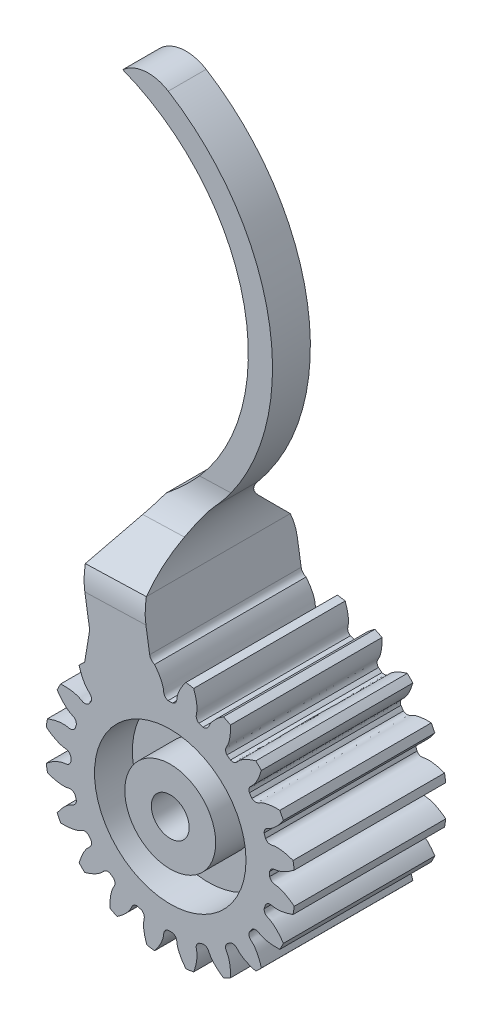
SolidWorks part; units mm, degrees
material "聚脂树脂"
ref_plane "前视基准面" through (0, 0, 0) normal (0, 0, 1) x (1, 0, 0)
ref_plane "上视基准面" through (0, 0, 0) normal (0, 1, 0) x (1, 0, 0)
ref_plane "右视基准面" through (0, 0, 0) normal (1, 0, 0) x (0, 0, -1)
other "Configuration Table"
sketch "草图1" plane through (0, 0, 0) normal (0, 0, 1) x (1, 0, 0)
  circle A0 centre (0, 0) radius 16.5
extrude "凸台-拉伸1" add sketch "草图1" along normal blind 20
ref_axis "基准轴1" through (0, 0, -1.5) along (0, 0, 1)
sketch "草图2" plane through (0, 0, 0) normal (0, 0, 1) x (1, 0, 0)
  line L0 (0, 0) -> (0, 16.5) construction
  circle A0 centre (0, 0) radius 16.5 construction
  arc A1 (0.29, 13.1218) -> (-0.29, 13.1218) centre (0, 0) ccw
  arc A2 (4.7717, 18.7474) -> (-4.7717, 18.7474) centre (0, 0) ccw
  spline S0 degree 3 poles (0.29, 13.1218) (0.9168, 13.3402) (0.8356, 13.7807) (0.9193, 14.205) (0.9283, 14.2463) (0.9395, 14.293) (0.9529, 14.3448) (0.969, 14.4018) (0.9878, 14.4638) (1.0095, 14.5309) (1.0345, 14.6028) (1.0629, 14.6795) (1.0948, 14.7608) (1.1305, 14.8467) (1.1702, 14.9371) (1.2141, 15.0317) (1.2623, 15.1305) (1.315, 15.2334) (1.3725, 15.3401) (1.4349, 15.4506) (1.5023, 15.5646) (1.575, 15.6821) (1.653, 15.8029) (1.7366, 15.9267) (1.826, 16.0534) (1.9211, 16.1829) (2.0223, 16.3149) (2.1296, 16.4493) (2.2432, 16.5859) (2.3632, 16.7244) (2.4897, 16.8646) (2.6229, 17.0065) (2.7628, 17.1496) (2.9095, 17.2939) (3.0632, 17.4391) (3.224, 17.585) (3.3918, 17.7313) (3.567, 17.8779) (3.7493, 18.0245) (3.9391, 18.1709) (4.1363, 18.3167) (4.4122, 18.5125) (4.6259, 18.6545) (4.7717, 18.7474) knots 0 0 0 0 0.165916 0.170906 0.176664 0.183189 0.190482 0.198542 0.207371 0.216967 0.22733 0.238462 0.250361 0.263027 0.276462 0.290664 0.305634 0.321371 0.337876 0.355149 0.37319 0.391998 0.411574 0.431917 0.453028 0.474907 0.497554 0.520968 0.54515 0.570099 0.595817 0.622302 0.649554 0.677575 0.706363 0.735918 0.766242 0.797333 0.829191 0.861818 0.895212 0.929373 1 1 1 1
  spline S1 degree 3 poles (-0.29, 13.1218) (-0.9168, 13.3402) (-0.8356, 13.7807) (-0.9193, 14.205) (-0.9283, 14.2463) (-0.9395, 14.293) (-0.9529, 14.3448) (-0.969, 14.4018) (-0.9878, 14.4638) (-1.0095, 14.5309) (-1.0345, 14.6028) (-1.0629, 14.6795) (-1.0948, 14.7608) (-1.1305, 14.8467) (-1.1702, 14.9371) (-1.2141, 15.0317) (-1.2623, 15.1305) (-1.315, 15.2334) (-1.3725, 15.3401) (-1.4349, 15.4506) (-1.5023, 15.5646) (-1.575, 15.6821) (-1.653, 15.8029) (-1.7366, 15.9267) (-1.826, 16.0534) (-1.9211, 16.1829) (-2.0223, 16.3149) (-2.1296, 16.4493) (-2.2432, 16.5859) (-2.3632, 16.7244) (-2.4897, 16.8646) (-2.6229, 17.0065) (-2.7628, 17.1496) (-2.9095, 17.2939) (-3.0632, 17.4391) (-3.224, 17.585) (-3.3918, 17.7313) (-3.567, 17.8779) (-3.7493, 18.0245) (-3.9391, 18.1709) (-4.1363, 18.3167) (-4.4122, 18.5125) (-4.6259, 18.6545) (-4.7717, 18.7474) knots 0 0 0 0 0.165916 0.170906 0.176664 0.183189 0.190482 0.198542 0.207371 0.216967 0.22733 0.238462 0.250361 0.263027 0.276462 0.290664 0.305634 0.321371 0.337876 0.355149 0.37319 0.391998 0.411574 0.431917 0.453028 0.474907 0.497554 0.520968 0.54515 0.570099 0.595817 0.622302 0.649554 0.677575 0.706363 0.735918 0.766242 0.797333 0.829191 0.861818 0.895212 0.929373 1 1 1 1
extrude "切除-拉伸1" cut sketch "草图2" along normal through all
pattern_circular "阵列(圆周)1" count 20 over 360 about axis through (0, 0, -1.5) along (0, 0, 1) of "切除-拉伸1"
sketch "草图3" plane through (0, 0, 0) normal (0, 0, 1) x (1, 0, 0)
  circle A0 centre (0, 0) radius 15 construction
  dimension "Dn" = 30
sketch "草图4" plane through (0, 0, 20) normal (0, 0, 1) x (1, 0, 0)
  line L0 (0, 0) -> (0, 24.252) construction
  line L1 (0, 0) -> (-4.1504, 26.2048) construction
  line L2 (-14.6667, -3.2847) -> (-22.6322, 47.0071) construction
  line L3 (-12.3599, 26.8976) -> (-7.9015, -1.2515)
  line L4 (-4.4584, 28.1491) -> (0, 0)
  line L5 (-15.1584, 78.5964) -> (-13.768, 74.7667)
  line L6 (-11.294, 12.029) -> (-10.6385, 16.029)
  line L7 (-3.0932, 16.2075) -> (-2.5812, 16.2969)
  line L8 (0, 0) -> (-34.8237, -5.5155) construction
  line L9 (-7.9015, -1.2515) -> (0, 0)
  circle A0 centre (0, 0) radius 12.5 construction
  circle A1 centre (-23.1908, 50.5343) radius 29.189 construction
  arc A2 (-2.0665, 16.3701) -> (-3.0932, 16.2075) centre (0, 0) ccw construction
  arc A3 (-4.4584, 28.1491) -> (-15.1584, 78.5964) centre (-23.1908, 50.5343) ccw
  circle A4 centre (-23.1908, 50.5343) radius 26 construction
  arc A6 (-12.3599, 26.8976) -> (-13.768, 74.7667) centre (-23.1908, 50.5343) ccw
  arc A8 (-3.7791, 12.5692) -> (-4.3306, 12.39) centre (0, 0) ccw construction
  arc A9 (-7.024, 14.9303) -> (-7.9502, 14.4584) centre (0, 0) ccw construction
  arc A10 (-7.4782, 10.7862) -> (-7.9474, 10.4453) centre (0, 0) ccw construction
  arc A12 (-3.7791, 12.5692) -> (-4.3306, 12.39) centre (0, 0) ccw
  arc A13 (-7.024, 14.9303) -> (-7.9502, 14.4584) centre (0, 0) ccw
  arc A14 (-7.4782, 10.7862) -> (-7.9474, 10.4453) centre (0, 0) ccw
  spline S0 degree 3 poles (1533.8481, 1281.675) (-100.0743, -100.0538) (-37.3462, 19.765) (-11.0168, 11.9483) (-10.7713, 11.8675) (-10.4966, 11.7648) (-10.2471, 11.6599) (-10.0224, 11.5547) (-9.822, 11.4509) (-9.671, 11.3649) (-9.5386, 11.2841) (-9.4441, 11.2225) (-9.3578, 11.1623) (-9.3008, 11.1209) (-9.2491, 11.0817) (-9.2026, 11.0451) (-9.1503, 11.0021) (-9.105, 10.9626) (-5.12, 7.2674) (-20.1054, -16.3486) (1244.1384, 1569.7336) knots -10.650201 -10.650201 -10.650201 -10.650201 0.502446 0.525093 0.568083 0.608002 0.644851 0.678629 0.709336 0.736973 0.749639 0.77267 0.783033 0.792629 0.801458 0.809518 0.816811 0.829094 0.834084 3.036535 3.036535 3.036535 3.036535 only from (-11.294, 12.029) to (-7.9474, 10.4453) construction
  spline S1 degree 3 poles (-2001.2932, -83.8658) (25.0446, 6.6561) (-2.87, 8.4138) (-3.5171, 13.8097) (-3.5224, 13.8696) (-3.5265, 13.9372) (-3.5289, 13.9963) (-3.5307, 14.0865) (-3.5293, 14.2134) (-3.5206, 14.3824) (-3.5033, 14.5733) (-3.4754, 14.7858) (-3.4352, 15.0192) (-3.381, 15.2729) (-3.3111, 15.5461) (-3.2398, 15.7847) (-3.1737, 15.9845) (5.9613, 41.8314) (139.7678, 22.1516) (-1938.4783, -487.5615) knots -2.036559 -2.036559 -2.036559 -2.036559 0.165916 0.170906 0.183189 0.190482 0.198542 0.207371 0.22733 0.250361 0.276462 0.305634 0.337876 0.37319 0.411574 0.453028 0.474907 0.497554 11.650216 11.650216 11.650216 11.650216 only from (-3.7791, 12.5692) to (-3.0932, 16.2075) construction
  spline S2 degree 3 poles (1854.8356, 744.9602) (-126.0947, -64.2322) (-29.4106, 30.3383) (-6.7853, 14.7679) (-6.5768, 14.6152) (-6.3474, 14.4326) (-6.1425, 14.2557) (-5.9612, 14.0862) (-5.8028, 13.9257) (-5.6857, 13.7971) (-5.5848, 13.6794) (-5.514, 13.5916) (-5.4504, 13.5077) (-5.409, 13.4507) (-5.3719, 13.3975) (-5.3391, 13.3482) (-5.3027, 13.2912) (-5.2717, 13.2396) (-2.6237, 8.4939) (-24.1734, -9.3355) (1668.3203, 1108.4455) knots -10.650201 -10.650201 -10.650201 -10.650201 0.502446 0.525093 0.568083 0.608002 0.644851 0.678629 0.709336 0.736973 0.749639 0.77267 0.783033 0.792629 0.801458 0.809518 0.816811 0.829094 0.834084 3.036535 3.036535 3.036535 3.036535 only from (-7.024, 14.9303) to (-4.3306, 12.39) construction
  spline S3 degree 3 poles (-1877.4269, -698.1947) (21.762, 14.0695) (-5.3295, 7.1151) (-7.6124, 12.047) (-7.636, 12.1023) (-7.6607, 12.1653) (-7.6812, 12.2208) (-7.7108, 12.3061) (-7.7487, 12.4272) (-7.7927, 12.5905) (-7.8352, 12.7775) (-7.8743, 12.9882) (-7.9082, 13.2226) (-7.9351, 13.4806) (-7.9531, 13.762) (-7.959, 14.011) (-7.9578, 14.2215) (-7.257, 41.6261) (126.0819, 64.2581) (-1692.9376, -1062.7213) knots -2.036559 -2.036559 -2.036559 -2.036559 0.165916 0.170906 0.183189 0.190482 0.198542 0.207371 0.22733 0.250361 0.276462 0.305634 0.337876 0.37319 0.411574 0.453028 0.474907 0.497554 11.650216 11.650216 11.650216 11.650216 only from (-7.4782, 10.7862) to (-7.9502, 14.4584) construction
  spline S4 degree 3 poles (-3.7791, 12.5692) (-3.2504, 12.9706) (-3.4637, 13.3644) (-3.5171, 13.8097) (-3.5224, 13.8696) (-3.5265, 13.9372) (-3.5289, 13.9963) (-3.5307, 14.0865) (-3.5293, 14.2134) (-3.5206, 14.3824) (-3.5033, 14.5733) (-3.4754, 14.7858) (-3.4352, 15.0192) (-3.381, 15.2729) (-3.3111, 15.5461) (-3.224, 15.8378) (-3.1479, 16.0599) (-3.1017, 16.1848) (-3.0932, 16.2075) knots 0 0 0 0 0.165916 0.170906 0.183189 0.190482 0.198542 0.207371 0.22733 0.250361 0.276462 0.305634 0.337876 0.37319 0.411574 0.453028 0.497554 0.507432 0.507432 0.507432 0.507432
  spline S5 degree 3 poles (-7.024, 14.9303) (-6.9129, 14.8568) (-6.7202, 14.7228) (-6.459, 14.5233) (-6.2419, 14.3433) (-6.0489, 14.1699) (-5.8792, 14.0047) (-5.7318, 13.8492) (-5.6234, 13.7255) (-5.5309, 13.613) (-5.4664, 13.5298) (-5.409, 13.4507) (-5.3719, 13.3975) (-5.3391, 13.3482) (-5.3027, 13.2912) (-5.2717, 13.2396) (-5.0532, 12.848) (-4.9943, 12.404) (-4.3306, 12.39) knots 0.492568 0.492568 0.492568 0.492568 0.546972 0.588426 0.62681 0.662124 0.694366 0.723538 0.749639 0.761538 0.783033 0.792629 0.801458 0.809518 0.816811 0.829094 0.834084 1 1 1 1
  spline S6 degree 3 poles (-7.4782, 10.7862) (-7.0995, 11.3313) (-7.424, 11.64) (-7.6124, 12.047) (-7.636, 12.1023) (-7.6607, 12.1653) (-7.6812, 12.2208) (-7.7108, 12.3061) (-7.7487, 12.4272) (-7.7927, 12.5905) (-7.8352, 12.7775) (-7.8743, 12.9882) (-7.9082, 13.2226) (-7.9351, 13.4806) (-7.9531, 13.762) (-7.9603, 14.0664) (-7.9566, 14.3011) (-7.9513, 14.4342) (-7.9502, 14.4584) knots 0 0 0 0 0.165916 0.170906 0.183189 0.190482 0.198542 0.207371 0.22733 0.250361 0.276462 0.305634 0.337876 0.37319 0.411574 0.453028 0.497554 0.507432 0.507432 0.507432 0.507432
  spline S7 degree 3 poles (-11.294, 12.029) (-11.1656, 11.9934) (-10.9409, 11.9255) (-10.6308, 11.8165) (-10.3687, 11.7125) (-10.1316, 11.6072) (-9.9192, 11.5025) (-9.7309, 11.4002) (-9.5896, 11.316) (-9.4669, 11.2376) (-9.3798, 11.1783) (-9.3008, 11.1209) (-9.2491, 11.0817) (-9.2026, 11.0451) (-9.1503, 11.0021) (-9.105, 10.9626) (-8.7761, 10.6576) (-8.5829, 10.2536) (-7.9474, 10.4453) knots 0.492568 0.492568 0.492568 0.492568 0.546972 0.588426 0.62681 0.662124 0.694366 0.723538 0.749639 0.761538 0.783033 0.792629 0.801458 0.809518 0.816811 0.829094 0.834084 1 1 1 1
  dimension "D6" = 52
  dimension "D7" = 76
  dimension "D5" = 28.5
  dimension "D10" = 25
  dimension "D9" = 80
  dimension "D1" = 9
  dimension "D2" = 15
  dimension "D3" = 8
  dimension "D4" = 28.5
  dimension "D8" = 4
extrude "凸台-拉伸2" add sketch "草图4" against normal blind 20 contours S7 A14 S6 A13 S5 A12 S4 L7 A6 | S7 region at (3.5117, 51.3198, 20) region at (-10.6183, 13.2048, 20)
fillet "圆角1" radius 1 1 edges
fillet "圆角2" radius 5 1 edges at (-15.1584, 78.5964, 10)
fillet "圆角4" radius 10 1 edges at (-4.4584, 28.1491, 10)
sketch "草图5" plane through (0, 0, 20) normal (0, 0, 1) x (1, 0, 0)
  circle A0 centre (0, 0) radius 2.5
  dimension "D1" = 5
extrude "切除-拉伸2" cut sketch "草图5" against normal blind 20
chamfer "倒角1" distance 5 angle 45 1 edges at (-12.3599, 26.8976, 10) first distance on face at (-11.4992, 21.4633, 10)
sketch "草图7" plane through (0, 0, 0) normal (0, 0, -1) x (-1, 0, 0)
  circle A0 centre (0, 0) radius 10
  dimension "D1" = 20
extrude "切除-拉伸3" cut sketch "草图7" against normal blind 3
sketch "草图8" plane through (0, 0, 20) normal (0, 0, 1) x (1, 0, 0)
  circle A0 centre (0, 0) radius 6
  circle A1 centre (0, 0) radius 10
  dimension "D1" = 12
  dimension "D2" = 20
extrude "切除-拉伸4" cut sketch "草图8" against normal blind 5
sketch "草图9" plane through (0, 0, 0) normal (1, 0, 0) x (0, 0, -1)
  line L0 (-10, 46.7) -> (-10, 64.7) construction
  line L5 (-13, 46.7) -> (-13, 64.7)
  line L6 (-7, 46.7) -> (-7, 64.7)
  line L7 (0, 31.2457) -> (0, 75.3118) construction
  arc A0 (-13, 46.7) -> (-7, 46.7) centre (-10, 46.7) ccw
  arc A1 (-7, 64.7) -> (-13, 64.7) centre (-10, 64.7) ccw
  point P2 (-10, 55.7)
  dimension "D2" = 3
  dimension "D1" = 18
  dimension "D3" = 10
  dimension "D4" = 55.7
sketch "草图10" plane through (0, 0, 0) normal (0, 0, -1) x (-1, 0, 0)
  line L0 (3.6544, 23.0732) -> (11.7149, 22.8255)
  line L4 (10.6385, 16.029) -> (11.7149, 22.8255)
  line L5 (11.7149, 22.8255) -> (7.3378, 29.9264)
  line L6 (3.6544, 23.0732) -> (2.7171, 17.1551)
  line L7 (11.294, 12.029) -> (10.6385, 16.029)
  line L8 (10.6385, 16.029) -> (11.7149, 22.8255)
  line L9 (11.7149, 22.8255) -> (7.3378, 29.9264)
  line L10 (3.6544, 23.0732) -> (2.7171, 17.1551)
  line L11 (11.294, 12.029) -> (10.6385, 16.029)
  arc A41 (13.768, 74.7667) -> (7.3378, 29.9264) centre (23.1908, 50.5343) ccw
  arc A42 (13.768, 74.7667) -> (7.7611, 75.3118) centre (10.4042, 71.0674) ccw
  arc A43 (7.7611, 75.3118) -> (1.283, 31.2457) centre (23.1908, 50.5343) ccw
  arc A44 (3.6544, 23.0732) -> (1.283, 31.2457) centre (-6.2224, 24.6376) ccw
  arc A45 (2.0665, 16.3701) -> (2.7171, 17.1551) centre (1.7294, 17.3115) ccw
  arc A46 (0.29, 13.1218) -> (-0.29, 13.1218) centre (0, 0) ccw
  arc A47 (-2.0665, 16.3701) -> (-3.0932, 16.2075) centre (0, 0) ccw
  arc A48 (-3.7791, 12.5692) -> (-4.3306, 12.39) centre (0, 0) ccw
  arc A49 (-7.024, 14.9303) -> (-7.9502, 14.4584) centre (0, 0) ccw
  arc A50 (-7.4782, 10.7862) -> (-7.9474, 10.4453) centre (0, 0) ccw
  arc A51 (-11.294, 12.029) -> (-12.029, 11.294) centre (0, 0) ccw
  arc A52 (-10.4453, 7.9474) -> (-10.7862, 7.4782) centre (0, 0) ccw
  arc A53 (-14.4584, 7.9502) -> (-14.9303, 7.024) centre (0, 0) ccw
  arc A54 (-12.39, 4.3306) -> (-12.5692, 3.7791) centre (0, 0) ccw
  arc A55 (-16.2075, 3.0932) -> (-16.3701, 2.0665) centre (0, 0) ccw
  arc A56 (-13.1218, 0.29) -> (-13.1218, -0.29) centre (0, 0) ccw
  arc A57 (-16.3701, -2.0665) -> (-16.2075, -3.0932) centre (0, 0) ccw
  arc A58 (-12.5692, -3.7791) -> (-12.39, -4.3306) centre (0, 0) ccw
  arc A59 (-14.9303, -7.024) -> (-14.4584, -7.9502) centre (0, 0) ccw
  arc A60 (-10.7862, -7.4782) -> (-10.4453, -7.9474) centre (0, 0) ccw
  arc A61 (-12.029, -11.294) -> (-11.294, -12.029) centre (0, 0) ccw
  arc A62 (-7.9474, -10.4453) -> (-7.4782, -10.7862) centre (0, 0) ccw
  arc A63 (-7.9502, -14.4584) -> (-7.024, -14.9303) centre (0, 0) ccw
  arc A64 (-4.3306, -12.39) -> (-3.7791, -12.5692) centre (0, 0) ccw
  arc A65 (-3.0932, -16.2075) -> (-2.0665, -16.3701) centre (0, 0) ccw
  arc A66 (-0.29, -13.1218) -> (0.29, -13.1218) centre (0, 0) ccw
  arc A67 (2.0665, -16.3701) -> (3.0932, -16.2075) centre (0, 0) ccw
  arc A68 (3.7791, -12.5692) -> (4.3306, -12.39) centre (0, 0) ccw
  arc A69 (7.024, -14.9303) -> (7.9502, -14.4584) centre (0, 0) ccw
  arc A70 (7.4782, -10.7862) -> (7.9474, -10.4453) centre (0, 0) ccw
  arc A71 (11.294, -12.029) -> (12.029, -11.294) centre (0, 0) ccw
  arc A72 (10.4453, -7.9474) -> (10.7862, -7.4782) centre (0, 0) ccw
  arc A73 (14.4584, -7.9502) -> (14.9303, -7.024) centre (0, 0) ccw
  arc A74 (12.39, -4.3306) -> (12.5692, -3.7791) centre (0, 0) ccw
  arc A75 (16.2075, -3.0932) -> (16.3701, -2.0665) centre (0, 0) ccw
  arc A76 (13.1218, -0.29) -> (13.1218, 0.29) centre (0, 0) ccw
  arc A77 (16.3701, 2.0665) -> (16.2075, 3.0932) centre (0, 0) ccw
  arc A78 (12.5692, 3.7791) -> (12.39, 4.3306) centre (0, 0) ccw
  arc A79 (14.9303, 7.024) -> (14.4584, 7.9502) centre (0, 0) ccw
  arc A80 (10.7862, 7.4782) -> (10.4453, 7.9474) centre (0, 0) ccw
  arc A81 (12.029, 11.294) -> (11.294, 12.029) centre (0, 0) ccw
  arc A82 (13.768, 74.7667) -> (7.3378, 29.9264) centre (23.1908, 50.5343) ccw
  arc A83 (13.768, 74.7667) -> (7.7611, 75.3118) centre (10.4042, 71.0674) ccw
  arc A84 (7.7611, 75.3118) -> (1.283, 31.2457) centre (23.1908, 50.5343) ccw
  arc A85 (3.6544, 23.0732) -> (1.283, 31.2457) centre (-6.2224, 24.6376) ccw
  arc A86 (2.0665, 16.3701) -> (2.7171, 17.1551) centre (1.7294, 17.3115) ccw
  arc A87 (0.29, 13.1218) -> (-0.29, 13.1218) centre (0, 0) ccw
  arc A88 (-2.0665, 16.3701) -> (-3.0932, 16.2075) centre (0, 0) ccw
  arc A89 (-3.7791, 12.5692) -> (-4.3306, 12.39) centre (0, 0) ccw
  arc A90 (-7.024, 14.9303) -> (-7.9502, 14.4584) centre (0, 0) ccw
  arc A91 (-7.4782, 10.7862) -> (-7.9474, 10.4453) centre (0, 0) ccw
  arc A92 (-11.294, 12.029) -> (-12.029, 11.294) centre (0, 0) ccw
  arc A93 (-10.4453, 7.9474) -> (-10.7862, 7.4782) centre (0, 0) ccw
  arc A94 (-14.4584, 7.9502) -> (-14.9303, 7.024) centre (0, 0) ccw
  arc A95 (-12.39, 4.3306) -> (-12.5692, 3.7791) centre (0, 0) ccw
  arc A96 (-16.2075, 3.0932) -> (-16.3701, 2.0665) centre (0, 0) ccw
  arc A97 (-13.1218, 0.29) -> (-13.1218, -0.29) centre (0, 0) ccw
  arc A98 (-16.3701, -2.0665) -> (-16.2075, -3.0932) centre (0, 0) ccw
  arc A99 (-12.5692, -3.7791) -> (-12.39, -4.3306) centre (0, 0) ccw
  arc A100 (-14.9303, -7.024) -> (-14.4584, -7.9502) centre (0, 0) ccw
  arc A101 (-10.7862, -7.4782) -> (-10.4453, -7.9474) centre (0, 0) ccw
  arc A102 (-12.029, -11.294) -> (-11.294, -12.029) centre (0, 0) ccw
  arc A103 (-7.9474, -10.4453) -> (-7.4782, -10.7862) centre (0, 0) ccw
  arc A104 (-7.9502, -14.4584) -> (-7.024, -14.9303) centre (0, 0) ccw
  arc A105 (-4.3306, -12.39) -> (-3.7791, -12.5692) centre (0, 0) ccw
  arc A106 (-3.0932, -16.2075) -> (-2.0665, -16.3701) centre (0, 0) ccw
  arc A107 (-0.29, -13.1218) -> (0.29, -13.1218) centre (0, 0) ccw
  arc A108 (2.0665, -16.3701) -> (3.0932, -16.2075) centre (0, 0) ccw
  arc A109 (3.7791, -12.5692) -> (4.3306, -12.39) centre (0, 0) ccw
  arc A110 (7.024, -14.9303) -> (7.9502, -14.4584) centre (0, 0) ccw
  arc A111 (7.4782, -10.7862) -> (7.9474, -10.4453) centre (0, 0) ccw
  arc A112 (11.294, -12.029) -> (12.029, -11.294) centre (0, 0) ccw
  arc A113 (10.4453, -7.9474) -> (10.7862, -7.4782) centre (0, 0) ccw
  arc A114 (14.4584, -7.9502) -> (14.9303, -7.024) centre (0, 0) ccw
  arc A115 (12.39, -4.3306) -> (12.5692, -3.7791) centre (0, 0) ccw
  arc A116 (16.2075, -3.0932) -> (16.3701, -2.0665) centre (0, 0) ccw
  arc A117 (13.1218, -0.29) -> (13.1218, 0.29) centre (0, 0) ccw
  arc A118 (16.3701, 2.0665) -> (16.2075, 3.0932) centre (0, 0) ccw
  arc A119 (12.5692, 3.7791) -> (12.39, 4.3306) centre (0, 0) ccw
  arc A120 (14.9303, 7.024) -> (14.4584, 7.9502) centre (0, 0) ccw
  arc A121 (10.7862, 7.4782) -> (10.4453, 7.9474) centre (0, 0) ccw
  arc A122 (12.029, 11.294) -> (11.294, 12.029) centre (0, 0) ccw
  spline S36 degree 3 poles (-3988.5857, 284.068) (202.7385, -48.5513) (20.2552, 42.738) (1.6549, 15.8084) (1.5041, 15.5702) (1.3741, 15.3456) (1.2638, 15.1361) (1.1716, 14.9426) (1.1068, 14.7914) (1.0536, 14.6559) (1.018, 14.5568) (0.9878, 14.4638) (0.969, 14.4018) (0.9529, 14.3448) (0.9359, 14.2793) (0.9224, 14.2207) (-0.397, 7.5331) (40.9433, -7.0017) (-3856.5787, 1071.6934) knots -12.739394 -12.739394 -12.739394 -12.739394 0.546972 0.588426 0.62681 0.662124 0.694366 0.723538 0.749639 0.761538 0.783033 0.792629 0.801458 0.809518 0.816811 0.829094 0.834084 3.601006 3.601006 3.601006 3.601006 only from (2.0665, 16.3701) to (0.29, 13.1218)
  spline S37 degree 3 poles (3856.2698, 1071.6079) (-40.9411, -7.001) (0.3969, 7.5333) (-0.9224, 14.2207) (-0.9359, 14.2793) (-0.9529, 14.3448) (-0.969, 14.4018) (-0.9951, 14.4881) (-1.0357, 14.6084) (-1.0961, 14.7664) (-1.1716, 14.9426) (-1.2638, 15.1361) (-1.3741, 15.3456) (-1.5041, 15.5702) (-1.6549, 15.8084) (-1.828, 16.0589) (-22.7654, 43.9229) (-212.0574, -60.1846) (3987.5666, 298.067) knots -2.600932 -2.600932 -2.600932 -2.600932 0.165916 0.170906 0.183189 0.190482 0.198542 0.207371 0.22733 0.250361 0.276462 0.305634 0.337876 0.37319 0.411574 0.453028 0.497554 14.645505 14.645505 14.645505 14.645505 only from (-0.29, 13.1218) to (-2.0665, 16.3701)
  spline S38 degree 3 poles (-3881.1522, -962.376) (207.8189, 16.4746) (6.057, 46.9055) (-3.3111, 15.5461) (-3.381, 15.2729) (-3.4352, 15.0192) (-3.4754, 14.7858) (-3.5033, 14.5733) (-3.5182, 14.4095) (-3.5269, 14.2641) (-3.5302, 14.1589) (-3.5302, 14.0612) (-3.5289, 13.9963) (-3.5265, 13.9372) (-3.5224, 13.8696) (-3.5171, 13.8097) (-2.7054, 7.0417) (41.1031, 5.9931) (-3998.9957, -172.5074) knots -12.739394 -12.739394 -12.739394 -12.739394 0.546972 0.588426 0.62681 0.662124 0.694366 0.723538 0.749639 0.761538 0.783033 0.792629 0.801458 0.809518 0.816811 0.829094 0.834084 3.601006 3.601006 3.601006 3.601006 only from (-3.0932, 16.2075) to (-3.7791, 12.5692)
  spline S39 degree 3 poles (3336.3854, 2210.8126) (-36.7739, -19.3098) (-1.9504, 7.2872) (-5.2717, 13.2396) (-5.3027, 13.2912) (-5.3391, 13.3482) (-5.3719, 13.3975) (-5.4235, 13.4715) (-5.4992, 13.5733) (-5.6055, 13.705) (-5.7318, 13.8492) (-5.8792, 14.0047) (-6.0489, 14.1699) (-6.2419, 14.3433) (-6.459, 14.5233) (-6.701, 14.7081) (-35.2241, 34.7383) (-183.0805, -122.7683) (3700.2934, 1515.7044) knots -2.600932 -2.600932 -2.600932 -2.600932 0.165916 0.170906 0.183189 0.190482 0.198542 0.207371 0.22733 0.250361 0.276462 0.305634 0.337876 0.37319 0.411574 0.453028 0.497554 14.645505 14.645505 14.645505 14.645505 only from (-4.3306, 12.39) to (-7.024, 14.9303)
  spline S40 degree 3 poles (-3393.8046, -2114.616) (192.5566, 79.8879) (-8.734, 46.4815) (-7.9531, 13.762) (-7.9351, 13.4806) (-7.9082, 13.2226) (-7.8743, 12.9882) (-7.8352, 12.7775) (-7.7988, 12.6171) (-7.7621, 12.4761) (-7.7327, 12.375) (-7.7025, 12.2821) (-7.6812, 12.2208) (-7.6607, 12.1653) (-7.636, 12.1023) (-7.6124, 12.047) (-4.749, 5.8611) (37.2394, 18.4014) (-3749.9632, -1399.8219) knots -12.739394 -12.739394 -12.739394 -12.739394 0.546972 0.588426 0.62681 0.662124 0.694366 0.723538 0.749639 0.761538 0.783033 0.792629 0.801458 0.809518 0.816811 0.829094 0.834084 3.601006 3.601006 3.601006 3.601006 only from (-7.9502, 14.4584) to (-7.4782, 10.7862)
  spline S41 degree 3 poles (2489.9125, 3133.6075) (-29.007, -29.7285) (-4.1068, 6.3279) (-9.105, 10.9626) (-9.1503, 11.0021) (-9.2026, 11.0451) (-9.2491, 11.0817) (-9.321, 11.1362) (-9.4245, 11.2097) (-9.5662, 11.302) (-9.7309, 11.4002) (-9.9192, 11.5025) (-10.1316, 11.6072) (-10.3687, 11.7125) (-10.6308, 11.8165) (-10.9181, 11.9175) (-44.2348, 22.1532) (-136.1824, -173.3346) (3050.8097, 2584.9741) knots -2.600932 -2.600932 -2.600932 -2.600932 0.165916 0.170906 0.183189 0.190482 0.198542 0.207371 0.22733 0.250361 0.276462 0.305634 0.337876 0.37319 0.411574 0.453028 0.497554 14.645505 14.645505 14.645505 14.645505 only from (-7.9474, 10.4453) to (-11.294, 12.029)
  spline S42 degree 3 poles (-2574.2477, -3059.8626) (158.4455, 135.4812) (-22.6701, 41.5076) (-11.8165, 10.6308) (-11.7125, 10.3687) (-11.6072, 10.1316) (-11.5025, 9.9192) (-11.4002, 9.7309) (-11.316, 9.5896) (-11.2376, 9.4669) (-11.1783, 9.3798) (-11.1209, 9.3008) (-11.0817, 9.2491) (-11.0451, 9.2026) (-11.0021, 9.1503) (-10.9626, 9.105) (-6.3277, 4.1067) (29.7304, 29.0083) (-3133.8582, -2490.1121) knots -12.739394 -12.739394 -12.739394 -12.739394 0.546972 0.588426 0.62681 0.662124 0.694366 0.723538 0.749639 0.761538 0.783033 0.792629 0.801458 0.809518 0.816811 0.829094 0.834084 3.601006 3.601006 3.601006 3.601006 only from (-12.029, 11.294) to (-10.4453, 7.9474)
  spline S43 degree 3 poles (1399.7095, 3749.6631) (-18.4007, -37.2371) (-5.8612, 4.7491) (-12.047, 7.6124) (-12.1023, 7.636) (-12.1653, 7.6607) (-12.2208, 7.6812) (-12.3061, 7.7108) (-12.4272, 7.7487) (-12.5905, 7.7927) (-12.7775, 7.8352) (-12.9882, 7.8743) (-13.2226, 7.9082) (-13.4806, 7.9351) (-13.762, 7.9531) (-14.0664, 7.9603) (-48.9155, 7.3996) (-75.9539, -206.9336) (2102.6915, 3401.2085) knots -2.600932 -2.600932 -2.600932 -2.600932 0.165916 0.170906 0.183189 0.190482 0.198542 0.207371 0.22733 0.250361 0.276462 0.305634 0.337876 0.37319 0.411574 0.453028 0.497554 14.645505 14.645505 14.645505 14.645505 only from (-10.7862, 7.4782) to (-14.4584, 7.9502)
  spline S44 degree 3 poles (-1502.7055, -3705.5886) (108.8246, 177.8126) (-34.3871, 32.4706) (-14.5233, 6.459) (-14.3433, 6.2419) (-14.1699, 6.0489) (-14.0047, 5.8792) (-13.8492, 5.7318) (-13.7255, 5.6234) (-13.613, 5.5309) (-13.5298, 5.4664) (-13.4507, 5.409) (-13.3975, 5.3719) (-13.3482, 5.3391) (-13.2912, 5.3027) (-13.2396, 5.2717) (-7.2871, 1.9503) (19.3112, 36.7758) (-2210.9893, -3336.6528) knots -12.739394 -12.739394 -12.739394 -12.739394 0.546972 0.588426 0.62681 0.662124 0.694366 0.723538 0.749639 0.761538 0.783033 0.792629 0.801458 0.809518 0.816811 0.829094 0.834084 3.601006 3.601006 3.601006 3.601006 only from (-14.9303, 7.024) to (-12.39, 4.3306)
  spline S45 degree 3 poles (172.4932, 3998.6755) (-5.9932, -41.1008) (-7.0419, 2.7054) (-13.8097, 3.5171) (-13.8696, 3.5224) (-13.9372, 3.5265) (-13.9963, 3.5289) (-14.0865, 3.5307) (-14.2134, 3.5293) (-14.3824, 3.5206) (-14.5733, 3.5033) (-14.7858, 3.4754) (-15.0192, 3.4352) (-15.2729, 3.381) (-15.5461, 3.3111) (-15.8378, 3.224) (-48.808, -8.0783) (-8.2904, -220.2766) (948.7472, 3884.5089) knots -2.600932 -2.600932 -2.600932 -2.600932 0.165916 0.170906 0.183189 0.190482 0.198542 0.207371 0.22733 0.250361 0.276462 0.305634 0.337876 0.37319 0.411574 0.453028 0.497554 14.645505 14.645505 14.645505 14.645505 only from (-12.5692, 3.7791) to (-16.2075, 3.0932)
  spline S46 degree 3 poles (-284.068, -3988.5857) (48.5513, 202.7385) (-42.738, 20.2552) (-15.8084, 1.6549) (-15.5702, 1.5041) (-15.3456, 1.3741) (-15.1361, 1.2638) (-14.9426, 1.1716) (-14.7914, 1.1068) (-14.6559, 1.0536) (-14.5568, 1.018) (-14.4638, 0.9878) (-14.4018, 0.969) (-14.3448, 0.9529) (-14.2793, 0.9359) (-14.2207, 0.9224) (-7.5331, -0.397) (7.0017, 40.9433) (-1071.6934, -3856.5787) knots -12.739394 -12.739394 -12.739394 -12.739394 0.546972 0.588426 0.62681 0.662124 0.694366 0.723538 0.749639 0.761538 0.783033 0.792629 0.801458 0.809518 0.816811 0.829094 0.834084 3.601006 3.601006 3.601006 3.601006 only from (-16.3701, 2.0665) to (-13.1218, 0.29)
  spline S47 degree 3 poles (-1071.6079, 3856.2698) (7.001, -40.9411) (-7.5333, 0.3969) (-14.2207, -0.9224) (-14.2793, -0.9359) (-14.3448, -0.9529) (-14.4018, -0.969) (-14.4881, -0.9951) (-14.6084, -1.0357) (-14.7664, -1.0961) (-14.9426, -1.1716) (-15.1361, -1.2638) (-15.3456, -1.3741) (-15.5702, -1.5041) (-15.8084, -1.6549) (-16.0589, -1.828) (-43.9229, -22.7654) (60.1846, -212.0574) (-298.067, 3987.5666) knots -2.600932 -2.600932 -2.600932 -2.600932 0.165916 0.170906 0.183189 0.190482 0.198542 0.207371 0.22733 0.250361 0.276462 0.305634 0.337876 0.37319 0.411574 0.453028 0.497554 14.645505 14.645505 14.645505 14.645505 only from (-13.1218, -0.29) to (-16.3701, -2.0665)
  spline S48 degree 3 poles (962.376, -3881.1522) (-16.4746, 207.8189) (-46.9055, 6.057) (-15.5461, -3.3111) (-15.2729, -3.381) (-15.0192, -3.4352) (-14.7858, -3.4754) (-14.5733, -3.5033) (-14.4095, -3.5182) (-14.2641, -3.5269) (-14.1589, -3.5302) (-14.0612, -3.5302) (-13.9963, -3.5289) (-13.9372, -3.5265) (-13.8696, -3.5224) (-13.8097, -3.5171) (-7.0417, -2.7054) (-5.9931, 41.1031) (172.5074, -3998.9957) knots -12.739394 -12.739394 -12.739394 -12.739394 0.546972 0.588426 0.62681 0.662124 0.694366 0.723538 0.749639 0.761538 0.783033 0.792629 0.801458 0.809518 0.816811 0.829094 0.834084 3.601006 3.601006 3.601006 3.601006 only from (-16.2075, -3.0932) to (-12.5692, -3.7791)
  spline S49 degree 3 poles (-2210.8126, 3336.3854) (19.3098, -36.7739) (-7.2872, -1.9504) (-13.2396, -5.2717) (-13.2912, -5.3027) (-13.3482, -5.3391) (-13.3975, -5.3719) (-13.4715, -5.4235) (-13.5733, -5.4992) (-13.705, -5.6055) (-13.8492, -5.7318) (-14.0047, -5.8792) (-14.1699, -6.0489) (-14.3433, -6.2419) (-14.5233, -6.459) (-14.7081, -6.701) (-34.7383, -35.2241) (122.7683, -183.0805) (-1515.7044, 3700.2934) knots -2.600932 -2.600932 -2.600932 -2.600932 0.165916 0.170906 0.183189 0.190482 0.198542 0.207371 0.22733 0.250361 0.276462 0.305634 0.337876 0.37319 0.411574 0.453028 0.497554 14.645505 14.645505 14.645505 14.645505 only from (-12.39, -4.3306) to (-14.9303, -7.024)
  spline S50 degree 3 poles (2114.616, -3393.8046) (-79.8879, 192.5566) (-46.4815, -8.734) (-13.762, -7.9531) (-13.4806, -7.9351) (-13.2226, -7.9082) (-12.9882, -7.8743) (-12.7775, -7.8352) (-12.6171, -7.7988) (-12.4761, -7.7621) (-12.375, -7.7327) (-12.2821, -7.7025) (-12.2208, -7.6812) (-12.1653, -7.6607) (-12.1023, -7.636) (-12.047, -7.6124) (-5.8611, -4.749) (-18.4014, 37.2394) (1399.8219, -3749.9632) knots -12.739394 -12.739394 -12.739394 -12.739394 0.546972 0.588426 0.62681 0.662124 0.694366 0.723538 0.749639 0.761538 0.783033 0.792629 0.801458 0.809518 0.816811 0.829094 0.834084 3.601006 3.601006 3.601006 3.601006 only from (-14.4584, -7.9502) to (-10.7862, -7.4782)
  spline S51 degree 3 poles (-3133.6075, 2489.9125) (29.7285, -29.007) (-6.3279, -4.1068) (-10.9626, -9.105) (-11.0021, -9.1503) (-11.0451, -9.2026) (-11.0817, -9.2491) (-11.1362, -9.321) (-11.2097, -9.4245) (-11.302, -9.5662) (-11.4002, -9.7309) (-11.5025, -9.9192) (-11.6072, -10.1316) (-11.7125, -10.3687) (-11.8165, -10.6308) (-11.9175, -10.9181) (-22.1532, -44.2348) (173.3346, -136.1824) (-2584.9741, 3050.8097) knots -2.600932 -2.600932 -2.600932 -2.600932 0.165916 0.170906 0.183189 0.190482 0.198542 0.207371 0.22733 0.250361 0.276462 0.305634 0.337876 0.37319 0.411574 0.453028 0.497554 14.645505 14.645505 14.645505 14.645505 only from (-10.4453, -7.9474) to (-12.029, -11.294)
  spline S52 degree 3 poles (3059.8626, -2574.2477) (-135.4812, 158.4455) (-41.5076, -22.6701) (-10.6308, -11.8165) (-10.3687, -11.7125) (-10.1316, -11.6072) (-9.9192, -11.5025) (-9.7309, -11.4002) (-9.5896, -11.316) (-9.4669, -11.2376) (-9.3798, -11.1783) (-9.3008, -11.1209) (-9.2491, -11.0817) (-9.2026, -11.0451) (-9.1503, -11.0021) (-9.105, -10.9626) (-4.1067, -6.3277) (-29.0083, 29.7304) (2490.1121, -3133.8582) knots -12.739394 -12.739394 -12.739394 -12.739394 0.546972 0.588426 0.62681 0.662124 0.694366 0.723538 0.749639 0.761538 0.783033 0.792629 0.801458 0.809518 0.816811 0.829094 0.834084 3.601006 3.601006 3.601006 3.601006 only from (-11.294, -12.029) to (-7.9474, -10.4453)
  spline S53 degree 3 poles (-3749.6631, 1399.7095) (37.2371, -18.4007) (-4.7491, -5.8612) (-7.6124, -12.047) (-7.636, -12.1023) (-7.6607, -12.1653) (-7.6812, -12.2208) (-7.7108, -12.3061) (-7.7487, -12.4272) (-7.7927, -12.5905) (-7.8352, -12.7775) (-7.8743, -12.9882) (-7.9082, -13.2226) (-7.9351, -13.4806) (-7.9531, -13.762) (-7.9603, -14.0664) (-7.3996, -48.9155) (206.9336, -75.9539) (-3401.2085, 2102.6915) knots -2.600932 -2.600932 -2.600932 -2.600932 0.165916 0.170906 0.183189 0.190482 0.198542 0.207371 0.22733 0.250361 0.276462 0.305634 0.337876 0.37319 0.411574 0.453028 0.497554 14.645505 14.645505 14.645505 14.645505 only from (-7.4782, -10.7862) to (-7.9502, -14.4584)
  spline S54 degree 3 poles (3705.5886, -1502.7055) (-177.8126, 108.8246) (-32.4706, -34.3871) (-6.459, -14.5233) (-6.2419, -14.3433) (-6.0489, -14.1699) (-5.8792, -14.0047) (-5.7318, -13.8492) (-5.6234, -13.7255) (-5.5309, -13.613) (-5.4664, -13.5298) (-5.409, -13.4507) (-5.3719, -13.3975) (-5.3391, -13.3482) (-5.3027, -13.2912) (-5.2717, -13.2396) (-1.9503, -7.2871) (-36.7758, 19.3112) (3336.6528, -2210.9893) knots -12.739394 -12.739394 -12.739394 -12.739394 0.546972 0.588426 0.62681 0.662124 0.694366 0.723538 0.749639 0.761538 0.783033 0.792629 0.801458 0.809518 0.816811 0.829094 0.834084 3.601006 3.601006 3.601006 3.601006 only from (-7.024, -14.9303) to (-4.3306, -12.39)
  spline S55 degree 3 poles (-3998.6755, 172.4932) (41.1008, -5.9932) (-2.7054, -7.0419) (-3.5171, -13.8097) (-3.5224, -13.8696) (-3.5265, -13.9372) (-3.5289, -13.9963) (-3.5307, -14.0865) (-3.5293, -14.2134) (-3.5206, -14.3824) (-3.5033, -14.5733) (-3.4754, -14.7858) (-3.4352, -15.0192) (-3.381, -15.2729) (-3.3111, -15.5461) (-3.224, -15.8378) (8.0783, -48.808) (220.2766, -8.2904) (-3884.5089, 948.7472) knots -2.600932 -2.600932 -2.600932 -2.600932 0.165916 0.170906 0.183189 0.190482 0.198542 0.207371 0.22733 0.250361 0.276462 0.305634 0.337876 0.37319 0.411574 0.453028 0.497554 14.645505 14.645505 14.645505 14.645505 only from (-3.7791, -12.5692) to (-3.0932, -16.2075)
  spline S56 degree 3 poles (3988.5857, -284.068) (-202.7385, 48.5513) (-20.2552, -42.738) (-1.6549, -15.8084) (-1.5041, -15.5702) (-1.3741, -15.3456) (-1.2638, -15.1361) (-1.1716, -14.9426) (-1.1068, -14.7914) (-1.0536, -14.6559) (-1.018, -14.5568) (-0.9878, -14.4638) (-0.969, -14.4018) (-0.9529, -14.3448) (-0.9359, -14.2793) (-0.9224, -14.2207) (0.397, -7.5331) (-40.9433, 7.0017) (3856.5787, -1071.6934) knots -12.739394 -12.739394 -12.739394 -12.739394 0.546972 0.588426 0.62681 0.662124 0.694366 0.723538 0.749639 0.761538 0.783033 0.792629 0.801458 0.809518 0.816811 0.829094 0.834084 3.601006 3.601006 3.601006 3.601006 only from (-2.0665, -16.3701) to (-0.29, -13.1218)
  spline S57 degree 3 poles (-3856.2698, -1071.6079) (40.9411, 7.001) (-0.3969, -7.5333) (0.9224, -14.2207) (0.9359, -14.2793) (0.9529, -14.3448) (0.969, -14.4018) (0.9951, -14.4881) (1.0357, -14.6084) (1.0961, -14.7664) (1.1716, -14.9426) (1.2638, -15.1361) (1.3741, -15.3456) (1.5041, -15.5702) (1.6549, -15.8084) (1.828, -16.0589) (22.7654, -43.9229) (212.0574, 60.1846) (-3987.5666, -298.067) knots -2.600932 -2.600932 -2.600932 -2.600932 0.165916 0.170906 0.183189 0.190482 0.198542 0.207371 0.22733 0.250361 0.276462 0.305634 0.337876 0.37319 0.411574 0.453028 0.497554 14.645505 14.645505 14.645505 14.645505 only from (0.29, -13.1218) to (2.0665, -16.3701)
  spline S58 degree 3 poles (3881.1522, 962.376) (-207.8189, -16.4746) (-6.057, -46.9055) (3.3111, -15.5461) (3.381, -15.2729) (3.4352, -15.0192) (3.4754, -14.7858) (3.5033, -14.5733) (3.5182, -14.4095) (3.5269, -14.2641) (3.5302, -14.1589) (3.5302, -14.0612) (3.5289, -13.9963) (3.5265, -13.9372) (3.5224, -13.8696) (3.5171, -13.8097) (2.7054, -7.0417) (-41.1031, -5.9931) (3998.9957, 172.5074) knots -12.739394 -12.739394 -12.739394 -12.739394 0.546972 0.588426 0.62681 0.662124 0.694366 0.723538 0.749639 0.761538 0.783033 0.792629 0.801458 0.809518 0.816811 0.829094 0.834084 3.601006 3.601006 3.601006 3.601006 only from (3.0932, -16.2075) to (3.7791, -12.5692)
  spline S59 degree 3 poles (-3336.3854, -2210.8126) (36.7739, 19.3098) (1.9504, -7.2872) (5.2717, -13.2396) (5.3027, -13.2912) (5.3391, -13.3482) (5.3719, -13.3975) (5.4235, -13.4715) (5.4992, -13.5733) (5.6055, -13.705) (5.7318, -13.8492) (5.8792, -14.0047) (6.0489, -14.1699) (6.2419, -14.3433) (6.459, -14.5233) (6.701, -14.7081) (35.2241, -34.7383) (183.0805, 122.7683) (-3700.2934, -1515.7044) knots -2.600932 -2.600932 -2.600932 -2.600932 0.165916 0.170906 0.183189 0.190482 0.198542 0.207371 0.22733 0.250361 0.276462 0.305634 0.337876 0.37319 0.411574 0.453028 0.497554 14.645505 14.645505 14.645505 14.645505 only from (4.3306, -12.39) to (7.024, -14.9303)
  spline S60 degree 3 poles (3393.8046, 2114.616) (-192.5566, -79.8879) (8.734, -46.4815) (7.9531, -13.762) (7.9351, -13.4806) (7.9082, -13.2226) (7.8743, -12.9882) (7.8352, -12.7775) (7.7988, -12.6171) (7.7621, -12.4761) (7.7327, -12.375) (7.7025, -12.2821) (7.6812, -12.2208) (7.6607, -12.1653) (7.636, -12.1023) (7.6124, -12.047) (4.749, -5.8611) (-37.2394, -18.4014) (3749.9632, 1399.8219) knots -12.739394 -12.739394 -12.739394 -12.739394 0.546972 0.588426 0.62681 0.662124 0.694366 0.723538 0.749639 0.761538 0.783033 0.792629 0.801458 0.809518 0.816811 0.829094 0.834084 3.601006 3.601006 3.601006 3.601006 only from (7.9502, -14.4584) to (7.4782, -10.7862)
  spline S61 degree 3 poles (-2489.9125, -3133.6075) (29.007, 29.7285) (4.1068, -6.3279) (9.105, -10.9626) (9.1503, -11.0021) (9.2026, -11.0451) (9.2491, -11.0817) (9.321, -11.1362) (9.4245, -11.2097) (9.5662, -11.302) (9.7309, -11.4002) (9.9192, -11.5025) (10.1316, -11.6072) (10.3687, -11.7125) (10.6308, -11.8165) (10.9181, -11.9175) (44.2348, -22.1532) (136.1824, 173.3346) (-3050.8097, -2584.9741) knots -2.600932 -2.600932 -2.600932 -2.600932 0.165916 0.170906 0.183189 0.190482 0.198542 0.207371 0.22733 0.250361 0.276462 0.305634 0.337876 0.37319 0.411574 0.453028 0.497554 14.645505 14.645505 14.645505 14.645505 only from (7.9474, -10.4453) to (11.294, -12.029)
  spline S62 degree 3 poles (2574.2477, 3059.8626) (-158.4455, -135.4812) (22.6701, -41.5076) (11.8165, -10.6308) (11.7125, -10.3687) (11.6072, -10.1316) (11.5025, -9.9192) (11.4002, -9.7309) (11.316, -9.5896) (11.2376, -9.4669) (11.1783, -9.3798) (11.1209, -9.3008) (11.0817, -9.2491) (11.0451, -9.2026) (11.0021, -9.1503) (10.9626, -9.105) (6.3277, -4.1067) (-29.7304, -29.0083) (3133.8582, 2490.1121) knots -12.739394 -12.739394 -12.739394 -12.739394 0.546972 0.588426 0.62681 0.662124 0.694366 0.723538 0.749639 0.761538 0.783033 0.792629 0.801458 0.809518 0.816811 0.829094 0.834084 3.601006 3.601006 3.601006 3.601006 only from (12.029, -11.294) to (10.4453, -7.9474)
  spline S63 degree 3 poles (-1399.7095, -3749.6631) (18.4007, 37.2371) (5.8612, -4.7491) (12.047, -7.6124) (12.1023, -7.636) (12.1653, -7.6607) (12.2208, -7.6812) (12.3061, -7.7108) (12.4272, -7.7487) (12.5905, -7.7927) (12.7775, -7.8352) (12.9882, -7.8743) (13.2226, -7.9082) (13.4806, -7.9351) (13.762, -7.9531) (14.0664, -7.9603) (48.9155, -7.3996) (75.9539, 206.9336) (-2102.6915, -3401.2085) knots -2.600932 -2.600932 -2.600932 -2.600932 0.165916 0.170906 0.183189 0.190482 0.198542 0.207371 0.22733 0.250361 0.276462 0.305634 0.337876 0.37319 0.411574 0.453028 0.497554 14.645505 14.645505 14.645505 14.645505 only from (10.7862, -7.4782) to (14.4584, -7.9502)
  spline S64 degree 3 poles (1502.7055, 3705.5886) (-108.8246, -177.8126) (34.3871, -32.4706) (14.5233, -6.459) (14.3433, -6.2419) (14.1699, -6.0489) (14.0047, -5.8792) (13.8492, -5.7318) (13.7255, -5.6234) (13.613, -5.5309) (13.5298, -5.4664) (13.4507, -5.409) (13.3975, -5.3719) (13.3482, -5.3391) (13.2912, -5.3027) (13.2396, -5.2717) (7.2871, -1.9503) (-19.3112, -36.7758) (2210.9893, 3336.6528) knots -12.739394 -12.739394 -12.739394 -12.739394 0.546972 0.588426 0.62681 0.662124 0.694366 0.723538 0.749639 0.761538 0.783033 0.792629 0.801458 0.809518 0.816811 0.829094 0.834084 3.601006 3.601006 3.601006 3.601006 only from (14.9303, -7.024) to (12.39, -4.3306)
  spline S65 degree 3 poles (-172.4932, -3998.6755) (5.9932, 41.1008) (7.0419, -2.7054) (13.8097, -3.5171) (13.8696, -3.5224) (13.9372, -3.5265) (13.9963, -3.5289) (14.0865, -3.5307) (14.2134, -3.5293) (14.3824, -3.5206) (14.5733, -3.5033) (14.7858, -3.4754) (15.0192, -3.4352) (15.2729, -3.381) (15.5461, -3.3111) (15.8378, -3.224) (48.808, 8.0783) (8.2904, 220.2766) (-948.7472, -3884.5089) knots -2.600932 -2.600932 -2.600932 -2.600932 0.165916 0.170906 0.183189 0.190482 0.198542 0.207371 0.22733 0.250361 0.276462 0.305634 0.337876 0.37319 0.411574 0.453028 0.497554 14.645505 14.645505 14.645505 14.645505 only from (12.5692, -3.7791) to (16.2075, -3.0932)
  spline S66 degree 3 poles (284.068, 3988.5857) (-48.5513, -202.7385) (42.738, -20.2552) (15.8084, -1.6549) (15.5702, -1.5041) (15.3456, -1.3741) (15.1361, -1.2638) (14.9426, -1.1716) (14.7914, -1.1068) (14.6559, -1.0536) (14.5568, -1.018) (14.4638, -0.9878) (14.4018, -0.969) (14.3448, -0.9529) (14.2793, -0.9359) (14.2207, -0.9224) (7.5331, 0.397) (-7.0017, -40.9433) (1071.6934, 3856.5787) knots -12.739394 -12.739394 -12.739394 -12.739394 0.546972 0.588426 0.62681 0.662124 0.694366 0.723538 0.749639 0.761538 0.783033 0.792629 0.801458 0.809518 0.816811 0.829094 0.834084 3.601006 3.601006 3.601006 3.601006 only from (16.3701, -2.0665) to (13.1218, -0.29)
  spline S67 degree 3 poles (1071.6079, -3856.2698) (-7.001, 40.9411) (7.5333, -0.3969) (14.2207, 0.9224) (14.2793, 0.9359) (14.3448, 0.9529) (14.4018, 0.969) (14.4881, 0.9951) (14.6084, 1.0357) (14.7664, 1.0961) (14.9426, 1.1716) (15.1361, 1.2638) (15.3456, 1.3741) (15.5702, 1.5041) (15.8084, 1.6549) (16.0589, 1.828) (43.9229, 22.7654) (-60.1846, 212.0574) (298.067, -3987.5666) knots -2.600932 -2.600932 -2.600932 -2.600932 0.165916 0.170906 0.183189 0.190482 0.198542 0.207371 0.22733 0.250361 0.276462 0.305634 0.337876 0.37319 0.411574 0.453028 0.497554 14.645505 14.645505 14.645505 14.645505 only from (13.1218, 0.29) to (16.3701, 2.0665)
  spline S68 degree 3 poles (-962.376, 3881.1522) (16.4746, -207.8189) (46.9055, -6.057) (15.5461, 3.3111) (15.2729, 3.381) (15.0192, 3.4352) (14.7858, 3.4754) (14.5733, 3.5033) (14.4095, 3.5182) (14.2641, 3.5269) (14.1589, 3.5302) (14.0612, 3.5302) (13.9963, 3.5289) (13.9372, 3.5265) (13.8696, 3.5224) (13.8097, 3.5171) (7.0417, 2.7054) (5.9931, -41.1031) (-172.5074, 3998.9957) knots -12.739394 -12.739394 -12.739394 -12.739394 0.546972 0.588426 0.62681 0.662124 0.694366 0.723538 0.749639 0.761538 0.783033 0.792629 0.801458 0.809518 0.816811 0.829094 0.834084 3.601006 3.601006 3.601006 3.601006 only from (16.2075, 3.0932) to (12.5692, 3.7791)
  spline S69 degree 3 poles (2210.8126, -3336.3854) (-19.3098, 36.7739) (7.2872, 1.9504) (13.2396, 5.2717) (13.2912, 5.3027) (13.3482, 5.3391) (13.3975, 5.3719) (13.4715, 5.4235) (13.5733, 5.4992) (13.705, 5.6055) (13.8492, 5.7318) (14.0047, 5.8792) (14.1699, 6.0489) (14.3433, 6.2419) (14.5233, 6.459) (14.7081, 6.701) (34.7383, 35.2241) (-122.7683, 183.0805) (1515.7044, -3700.2934) knots -2.600932 -2.600932 -2.600932 -2.600932 0.165916 0.170906 0.183189 0.190482 0.198542 0.207371 0.22733 0.250361 0.276462 0.305634 0.337876 0.37319 0.411574 0.453028 0.497554 14.645505 14.645505 14.645505 14.645505 only from (12.39, 4.3306) to (14.9303, 7.024)
  spline S70 degree 3 poles (-2114.616, 3393.8046) (79.8879, -192.5566) (46.4815, 8.734) (13.762, 7.9531) (13.4806, 7.9351) (13.2226, 7.9082) (12.9882, 7.8743) (12.7775, 7.8352) (12.6171, 7.7988) (12.4761, 7.7621) (12.375, 7.7327) (12.2821, 7.7025) (12.2208, 7.6812) (12.1653, 7.6607) (12.1023, 7.636) (12.047, 7.6124) (5.8611, 4.749) (18.4014, -37.2394) (-1399.8219, 3749.9632) knots -12.739394 -12.739394 -12.739394 -12.739394 0.546972 0.588426 0.62681 0.662124 0.694366 0.723538 0.749639 0.761538 0.783033 0.792629 0.801458 0.809518 0.816811 0.829094 0.834084 3.601006 3.601006 3.601006 3.601006 only from (14.4584, 7.9502) to (10.7862, 7.4782)
  spline S71 degree 3 poles (3133.6075, -2489.9125) (-29.7285, 29.007) (6.3279, 4.1068) (10.9626, 9.105) (11.0021, 9.1503) (11.0451, 9.2026) (11.0817, 9.2491) (11.1362, 9.321) (11.2097, 9.4245) (11.302, 9.5662) (11.4002, 9.7309) (11.5025, 9.9192) (11.6072, 10.1316) (11.7125, 10.3687) (11.8165, 10.6308) (11.9175, 10.9181) (22.1532, 44.2348) (-173.3346, 136.1824) (2584.9741, -3050.8097) knots -2.600932 -2.600932 -2.600932 -2.600932 0.165916 0.170906 0.183189 0.190482 0.198542 0.207371 0.22733 0.250361 0.276462 0.305634 0.337876 0.37319 0.411574 0.453028 0.497554 14.645505 14.645505 14.645505 14.645505 only from (10.4453, 7.9474) to (12.029, 11.294)
  spline S72 degree 3 poles (2.0665, 16.3701) (1.9836, 16.2659) (1.8417, 16.0788) (1.6549, 15.8084) (1.5041, 15.5702) (1.3741, 15.3456) (1.2638, 15.1361) (1.1716, 14.9426) (1.1068, 14.7914) (1.0536, 14.6559) (1.018, 14.5568) (0.9878, 14.4638) (0.969, 14.4018) (0.9529, 14.3448) (0.9359, 14.2793) (0.9224, 14.2207) (0.8356, 13.7807) (0.9168, 13.3402) (0.29, 13.1218) knots 0.492568 0.492568 0.492568 0.492568 0.546972 0.588426 0.62681 0.662124 0.694366 0.723538 0.749639 0.761538 0.783033 0.792629 0.801458 0.809518 0.816811 0.829094 0.834084 1 1 1 1
  spline S73 degree 3 poles (-0.29, 13.1218) (-0.9168, 13.3402) (-0.8356, 13.7807) (-0.9224, 14.2207) (-0.9359, 14.2793) (-0.9529, 14.3448) (-0.969, 14.4018) (-0.9951, 14.4881) (-1.0357, 14.6084) (-1.0961, 14.7664) (-1.1716, 14.9426) (-1.2638, 15.1361) (-1.3741, 15.3456) (-1.5041, 15.5702) (-1.6549, 15.8084) (-1.828, 16.0589) (-1.969, 16.2466) (-2.0515, 16.3512) (-2.0665, 16.3701) knots 0 0 0 0 0.165916 0.170906 0.183189 0.190482 0.198542 0.207371 0.22733 0.250361 0.276462 0.305634 0.337876 0.37319 0.411574 0.453028 0.497554 0.507432 0.507432 0.507432 0.507432
  spline S74 degree 3 poles (-3.0932, 16.2075) (-3.1399, 16.0827) (-3.217, 15.861) (-3.3111, 15.5461) (-3.381, 15.2729) (-3.4352, 15.0192) (-3.4754, 14.7858) (-3.5033, 14.5733) (-3.5182, 14.4095) (-3.5269, 14.2641) (-3.5302, 14.1589) (-3.5302, 14.0612) (-3.5289, 13.9963) (-3.5265, 13.9372) (-3.5224, 13.8696) (-3.5171, 13.8097) (-3.4637, 13.3644) (-3.2504, 12.9706) (-3.7791, 12.5692) knots 0.492568 0.492568 0.492568 0.492568 0.546972 0.588426 0.62681 0.662124 0.694366 0.723538 0.749639 0.761538 0.783033 0.792629 0.801458 0.809518 0.816811 0.829094 0.834084 1 1 1 1
  spline S75 degree 3 poles (-4.3306, 12.39) (-4.9943, 12.404) (-5.0532, 12.848) (-5.2717, 13.2396) (-5.3027, 13.2912) (-5.3391, 13.3482) (-5.3719, 13.3975) (-5.4235, 13.4715) (-5.4992, 13.5733) (-5.6055, 13.705) (-5.7318, 13.8492) (-5.8792, 14.0047) (-6.0489, 14.1699) (-6.2419, 14.3433) (-6.459, 14.5233) (-6.701, 14.7081) (-6.8931, 14.843) (-7.0039, 14.9169) (-7.024, 14.9303) knots 0 0 0 0 0.165916 0.170906 0.183189 0.190482 0.198542 0.207371 0.22733 0.250361 0.276462 0.305634 0.337876 0.37319 0.411574 0.453028 0.497554 0.507432 0.507432 0.507432 0.507432
  spline S76 degree 3 poles (-7.9502, 14.4584) (-7.9561, 14.3253) (-7.9609, 14.0906) (-7.9531, 13.762) (-7.9351, 13.4806) (-7.9082, 13.2226) (-7.8743, 12.9882) (-7.8352, 12.7775) (-7.7988, 12.6171) (-7.7621, 12.4761) (-7.7327, 12.375) (-7.7025, 12.2821) (-7.6812, 12.2208) (-7.6607, 12.1653) (-7.636, 12.1023) (-7.6124, 12.047) (-7.424, 11.64) (-7.0995, 11.3313) (-7.4782, 10.7862) knots 0.492568 0.492568 0.492568 0.492568 0.546972 0.588426 0.62681 0.662124 0.694366 0.723538 0.749639 0.761538 0.783033 0.792629 0.801458 0.809518 0.816811 0.829094 0.834084 1 1 1 1
  spline S77 degree 3 poles (-7.9474, 10.4453) (-8.5829, 10.2536) (-8.7761, 10.6576) (-9.105, 10.9626) (-9.1503, 11.0021) (-9.2026, 11.0451) (-9.2491, 11.0817) (-9.321, 11.1362) (-9.4245, 11.2097) (-9.5662, 11.302) (-9.7309, 11.4002) (-9.9192, 11.5025) (-10.1316, 11.6072) (-10.3687, 11.7125) (-10.6308, 11.8165) (-10.9181, 11.9175) (-11.1425, 11.9864) (-11.2707, 12.0225) (-11.294, 12.029) knots 0 0 0 0 0.165916 0.170906 0.183189 0.190482 0.198542 0.207371 0.22733 0.250361 0.276462 0.305634 0.337876 0.37319 0.411574 0.453028 0.497554 0.507432 0.507432 0.507432 0.507432
  spline S78 degree 3 poles (-12.029, 11.294) (-11.9934, 11.1656) (-11.9255, 10.9409) (-11.8165, 10.6308) (-11.7125, 10.3687) (-11.6072, 10.1316) (-11.5025, 9.9192) (-11.4002, 9.7309) (-11.316, 9.5896) (-11.2376, 9.4669) (-11.1783, 9.3798) (-11.1209, 9.3008) (-11.0817, 9.2491) (-11.0451, 9.2026) (-11.0021, 9.1503) (-10.9626, 9.105) (-10.6576, 8.7761) (-10.2536, 8.5829) (-10.4453, 7.9474) knots 0.492568 0.492568 0.492568 0.492568 0.546972 0.588426 0.62681 0.662124 0.694366 0.723538 0.749639 0.761538 0.783033 0.792629 0.801458 0.809518 0.816811 0.829094 0.834084 1 1 1 1
  spline S79 degree 3 poles (-10.7862, 7.4782) (-11.3313, 7.0995) (-11.64, 7.424) (-12.047, 7.6124) (-12.1023, 7.636) (-12.1653, 7.6607) (-12.2208, 7.6812) (-12.3061, 7.7108) (-12.4272, 7.7487) (-12.5905, 7.7927) (-12.7775, 7.8352) (-12.9882, 7.8743) (-13.2226, 7.9082) (-13.4806, 7.9351) (-13.762, 7.9531) (-14.0664, 7.9603) (-14.3011, 7.9566) (-14.4342, 7.9513) (-14.4584, 7.9502) knots 0 0 0 0 0.165916 0.170906 0.183189 0.190482 0.198542 0.207371 0.22733 0.250361 0.276462 0.305634 0.337876 0.37319 0.411574 0.453028 0.497554 0.507432 0.507432 0.507432 0.507432
  spline S80 degree 3 poles (-14.9303, 7.024) (-14.8568, 6.9129) (-14.7228, 6.7202) (-14.5233, 6.459) (-14.3433, 6.2419) (-14.1699, 6.0489) (-14.0047, 5.8792) (-13.8492, 5.7318) (-13.7255, 5.6234) (-13.613, 5.5309) (-13.5298, 5.4664) (-13.4507, 5.409) (-13.3975, 5.3719) (-13.3482, 5.3391) (-13.2912, 5.3027) (-13.2396, 5.2717) (-12.848, 5.0532) (-12.404, 4.9943) (-12.39, 4.3306) knots 0.492568 0.492568 0.492568 0.492568 0.546972 0.588426 0.62681 0.662124 0.694366 0.723538 0.749639 0.761538 0.783033 0.792629 0.801458 0.809518 0.816811 0.829094 0.834084 1 1 1 1
  spline S81 degree 3 poles (-12.5692, 3.7791) (-12.9706, 3.2504) (-13.3644, 3.4637) (-13.8097, 3.5171) (-13.8696, 3.5224) (-13.9372, 3.5265) (-13.9963, 3.5289) (-14.0865, 3.5307) (-14.2134, 3.5293) (-14.3824, 3.5206) (-14.5733, 3.5033) (-14.7858, 3.4754) (-15.0192, 3.4352) (-15.2729, 3.381) (-15.5461, 3.3111) (-15.8378, 3.224) (-16.0599, 3.1479) (-16.1848, 3.1017) (-16.2075, 3.0932) knots 0 0 0 0 0.165916 0.170906 0.183189 0.190482 0.198542 0.207371 0.22733 0.250361 0.276462 0.305634 0.337876 0.37319 0.411574 0.453028 0.497554 0.507432 0.507432 0.507432 0.507432
  spline S82 degree 3 poles (-16.3701, 2.0665) (-16.2659, 1.9836) (-16.0788, 1.8417) (-15.8084, 1.6549) (-15.5702, 1.5041) (-15.3456, 1.3741) (-15.1361, 1.2638) (-14.9426, 1.1716) (-14.7914, 1.1068) (-14.6559, 1.0536) (-14.5568, 1.018) (-14.4638, 0.9878) (-14.4018, 0.969) (-14.3448, 0.9529) (-14.2793, 0.9359) (-14.2207, 0.9224) (-13.7807, 0.8356) (-13.3402, 0.9168) (-13.1218, 0.29) knots 0.492568 0.492568 0.492568 0.492568 0.546972 0.588426 0.62681 0.662124 0.694366 0.723538 0.749639 0.761538 0.783033 0.792629 0.801458 0.809518 0.816811 0.829094 0.834084 1 1 1 1
  spline S83 degree 3 poles (-13.1218, -0.29) (-13.3402, -0.9168) (-13.7807, -0.8356) (-14.2207, -0.9224) (-14.2793, -0.9359) (-14.3448, -0.9529) (-14.4018, -0.969) (-14.4881, -0.9951) (-14.6084, -1.0357) (-14.7664, -1.0961) (-14.9426, -1.1716) (-15.1361, -1.2638) (-15.3456, -1.3741) (-15.5702, -1.5041) (-15.8084, -1.6549) (-16.0589, -1.828) (-16.2466, -1.969) (-16.3512, -2.0515) (-16.3701, -2.0665) knots 0 0 0 0 0.165916 0.170906 0.183189 0.190482 0.198542 0.207371 0.22733 0.250361 0.276462 0.305634 0.337876 0.37319 0.411574 0.453028 0.497554 0.507432 0.507432 0.507432 0.507432
  spline S84 degree 3 poles (-16.2075, -3.0932) (-16.0827, -3.1399) (-15.861, -3.217) (-15.5461, -3.3111) (-15.2729, -3.381) (-15.0192, -3.4352) (-14.7858, -3.4754) (-14.5733, -3.5033) (-14.4095, -3.5182) (-14.2641, -3.5269) (-14.1589, -3.5302) (-14.0612, -3.5302) (-13.9963, -3.5289) (-13.9372, -3.5265) (-13.8696, -3.5224) (-13.8097, -3.5171) (-13.3644, -3.4637) (-12.9706, -3.2504) (-12.5692, -3.7791) knots 0.492568 0.492568 0.492568 0.492568 0.546972 0.588426 0.62681 0.662124 0.694366 0.723538 0.749639 0.761538 0.783033 0.792629 0.801458 0.809518 0.816811 0.829094 0.834084 1 1 1 1
  spline S85 degree 3 poles (-12.39, -4.3306) (-12.404, -4.9943) (-12.848, -5.0532) (-13.2396, -5.2717) (-13.2912, -5.3027) (-13.3482, -5.3391) (-13.3975, -5.3719) (-13.4715, -5.4235) (-13.5733, -5.4992) (-13.705, -5.6055) (-13.8492, -5.7318) (-14.0047, -5.8792) (-14.1699, -6.0489) (-14.3433, -6.2419) (-14.5233, -6.459) (-14.7081, -6.701) (-14.843, -6.8931) (-14.9169, -7.0039) (-14.9303, -7.024) knots 0 0 0 0 0.165916 0.170906 0.183189 0.190482 0.198542 0.207371 0.22733 0.250361 0.276462 0.305634 0.337876 0.37319 0.411574 0.453028 0.497554 0.507432 0.507432 0.507432 0.507432
  spline S86 degree 3 poles (-14.4584, -7.9502) (-14.3253, -7.9561) (-14.0906, -7.9609) (-13.762, -7.9531) (-13.4806, -7.9351) (-13.2226, -7.9082) (-12.9882, -7.8743) (-12.7775, -7.8352) (-12.6171, -7.7988) (-12.4761, -7.7621) (-12.375, -7.7327) (-12.2821, -7.7025) (-12.2208, -7.6812) (-12.1653, -7.6607) (-12.1023, -7.636) (-12.047, -7.6124) (-11.64, -7.424) (-11.3313, -7.0995) (-10.7862, -7.4782) knots 0.492568 0.492568 0.492568 0.492568 0.546972 0.588426 0.62681 0.662124 0.694366 0.723538 0.749639 0.761538 0.783033 0.792629 0.801458 0.809518 0.816811 0.829094 0.834084 1 1 1 1
  spline S87 degree 3 poles (-10.4453, -7.9474) (-10.2536, -8.5829) (-10.6576, -8.7761) (-10.9626, -9.105) (-11.0021, -9.1503) (-11.0451, -9.2026) (-11.0817, -9.2491) (-11.1362, -9.321) (-11.2097, -9.4245) (-11.302, -9.5662) (-11.4002, -9.7309) (-11.5025, -9.9192) (-11.6072, -10.1316) (-11.7125, -10.3687) (-11.8165, -10.6308) (-11.9175, -10.9181) (-11.9864, -11.1425) (-12.0225, -11.2707) (-12.029, -11.294) knots 0 0 0 0 0.165916 0.170906 0.183189 0.190482 0.198542 0.207371 0.22733 0.250361 0.276462 0.305634 0.337876 0.37319 0.411574 0.453028 0.497554 0.507432 0.507432 0.507432 0.507432
  spline S88 degree 3 poles (-11.294, -12.029) (-11.1656, -11.9934) (-10.9409, -11.9255) (-10.6308, -11.8165) (-10.3687, -11.7125) (-10.1316, -11.6072) (-9.9192, -11.5025) (-9.7309, -11.4002) (-9.5896, -11.316) (-9.4669, -11.2376) (-9.3798, -11.1783) (-9.3008, -11.1209) (-9.2491, -11.0817) (-9.2026, -11.0451) (-9.1503, -11.0021) (-9.105, -10.9626) (-8.7761, -10.6576) (-8.5829, -10.2536) (-7.9474, -10.4453) knots 0.492568 0.492568 0.492568 0.492568 0.546972 0.588426 0.62681 0.662124 0.694366 0.723538 0.749639 0.761538 0.783033 0.792629 0.801458 0.809518 0.816811 0.829094 0.834084 1 1 1 1
  spline S89 degree 3 poles (-7.4782, -10.7862) (-7.0995, -11.3313) (-7.424, -11.64) (-7.6124, -12.047) (-7.636, -12.1023) (-7.6607, -12.1653) (-7.6812, -12.2208) (-7.7108, -12.3061) (-7.7487, -12.4272) (-7.7927, -12.5905) (-7.8352, -12.7775) (-7.8743, -12.9882) (-7.9082, -13.2226) (-7.9351, -13.4806) (-7.9531, -13.762) (-7.9603, -14.0664) (-7.9566, -14.3011) (-7.9513, -14.4342) (-7.9502, -14.4584) knots 0 0 0 0 0.165916 0.170906 0.183189 0.190482 0.198542 0.207371 0.22733 0.250361 0.276462 0.305634 0.337876 0.37319 0.411574 0.453028 0.497554 0.507432 0.507432 0.507432 0.507432
  spline S90 degree 3 poles (-7.024, -14.9303) (-6.9129, -14.8568) (-6.7202, -14.7228) (-6.459, -14.5233) (-6.2419, -14.3433) (-6.0489, -14.1699) (-5.8792, -14.0047) (-5.7318, -13.8492) (-5.6234, -13.7255) (-5.5309, -13.613) (-5.4664, -13.5298) (-5.409, -13.4507) (-5.3719, -13.3975) (-5.3391, -13.3482) (-5.3027, -13.2912) (-5.2717, -13.2396) (-5.0532, -12.848) (-4.9943, -12.404) (-4.3306, -12.39) knots 0.492568 0.492568 0.492568 0.492568 0.546972 0.588426 0.62681 0.662124 0.694366 0.723538 0.749639 0.761538 0.783033 0.792629 0.801458 0.809518 0.816811 0.829094 0.834084 1 1 1 1
  spline S91 degree 3 poles (-3.7791, -12.5692) (-3.2504, -12.9706) (-3.4637, -13.3644) (-3.5171, -13.8097) (-3.5224, -13.8696) (-3.5265, -13.9372) (-3.5289, -13.9963) (-3.5307, -14.0865) (-3.5293, -14.2134) (-3.5206, -14.3824) (-3.5033, -14.5733) (-3.4754, -14.7858) (-3.4352, -15.0192) (-3.381, -15.2729) (-3.3111, -15.5461) (-3.224, -15.8378) (-3.1479, -16.0599) (-3.1017, -16.1848) (-3.0932, -16.2075) knots 0 0 0 0 0.165916 0.170906 0.183189 0.190482 0.198542 0.207371 0.22733 0.250361 0.276462 0.305634 0.337876 0.37319 0.411574 0.453028 0.497554 0.507432 0.507432 0.507432 0.507432
  spline S92 degree 3 poles (-2.0665, -16.3701) (-1.9836, -16.2659) (-1.8417, -16.0788) (-1.6549, -15.8084) (-1.5041, -15.5702) (-1.3741, -15.3456) (-1.2638, -15.1361) (-1.1716, -14.9426) (-1.1068, -14.7914) (-1.0536, -14.6559) (-1.018, -14.5568) (-0.9878, -14.4638) (-0.969, -14.4018) (-0.9529, -14.3448) (-0.9359, -14.2793) (-0.9224, -14.2207) (-0.8356, -13.7807) (-0.9168, -13.3402) (-0.29, -13.1218) knots 0.492568 0.492568 0.492568 0.492568 0.546972 0.588426 0.62681 0.662124 0.694366 0.723538 0.749639 0.761538 0.783033 0.792629 0.801458 0.809518 0.816811 0.829094 0.834084 1 1 1 1
  spline S93 degree 3 poles (0.29, -13.1218) (0.9168, -13.3402) (0.8356, -13.7807) (0.9224, -14.2207) (0.9359, -14.2793) (0.9529, -14.3448) (0.969, -14.4018) (0.9951, -14.4881) (1.0357, -14.6084) (1.0961, -14.7664) (1.1716, -14.9426) (1.2638, -15.1361) (1.3741, -15.3456) (1.5041, -15.5702) (1.6549, -15.8084) (1.828, -16.0589) (1.969, -16.2466) (2.0515, -16.3512) (2.0665, -16.3701) knots 0 0 0 0 0.165916 0.170906 0.183189 0.190482 0.198542 0.207371 0.22733 0.250361 0.276462 0.305634 0.337876 0.37319 0.411574 0.453028 0.497554 0.507432 0.507432 0.507432 0.507432
  spline S94 degree 3 poles (3.0932, -16.2075) (3.1399, -16.0827) (3.217, -15.861) (3.3111, -15.5461) (3.381, -15.2729) (3.4352, -15.0192) (3.4754, -14.7858) (3.5033, -14.5733) (3.5182, -14.4095) (3.5269, -14.2641) (3.5302, -14.1589) (3.5302, -14.0612) (3.5289, -13.9963) (3.5265, -13.9372) (3.5224, -13.8696) (3.5171, -13.8097) (3.4637, -13.3644) (3.2504, -12.9706) (3.7791, -12.5692) knots 0.492568 0.492568 0.492568 0.492568 0.546972 0.588426 0.62681 0.662124 0.694366 0.723538 0.749639 0.761538 0.783033 0.792629 0.801458 0.809518 0.816811 0.829094 0.834084 1 1 1 1
  spline S95 degree 3 poles (4.3306, -12.39) (4.9943, -12.404) (5.0532, -12.848) (5.2717, -13.2396) (5.3027, -13.2912) (5.3391, -13.3482) (5.3719, -13.3975) (5.4235, -13.4715) (5.4992, -13.5733) (5.6055, -13.705) (5.7318, -13.8492) (5.8792, -14.0047) (6.0489, -14.1699) (6.2419, -14.3433) (6.459, -14.5233) (6.701, -14.7081) (6.8931, -14.843) (7.0039, -14.9169) (7.024, -14.9303) knots 0 0 0 0 0.165916 0.170906 0.183189 0.190482 0.198542 0.207371 0.22733 0.250361 0.276462 0.305634 0.337876 0.37319 0.411574 0.453028 0.497554 0.507432 0.507432 0.507432 0.507432
  spline S96 degree 3 poles (7.9502, -14.4584) (7.9561, -14.3253) (7.9609, -14.0906) (7.9531, -13.762) (7.9351, -13.4806) (7.9082, -13.2226) (7.8743, -12.9882) (7.8352, -12.7775) (7.7988, -12.6171) (7.7621, -12.4761) (7.7327, -12.375) (7.7025, -12.2821) (7.6812, -12.2208) (7.6607, -12.1653) (7.636, -12.1023) (7.6124, -12.047) (7.424, -11.64) (7.0995, -11.3313) (7.4782, -10.7862) knots 0.492568 0.492568 0.492568 0.492568 0.546972 0.588426 0.62681 0.662124 0.694366 0.723538 0.749639 0.761538 0.783033 0.792629 0.801458 0.809518 0.816811 0.829094 0.834084 1 1 1 1
  spline S97 degree 3 poles (7.9474, -10.4453) (8.5829, -10.2536) (8.7761, -10.6576) (9.105, -10.9626) (9.1503, -11.0021) (9.2026, -11.0451) (9.2491, -11.0817) (9.321, -11.1362) (9.4245, -11.2097) (9.5662, -11.302) (9.7309, -11.4002) (9.9192, -11.5025) (10.1316, -11.6072) (10.3687, -11.7125) (10.6308, -11.8165) (10.9181, -11.9175) (11.1425, -11.9864) (11.2707, -12.0225) (11.294, -12.029) knots 0 0 0 0 0.165916 0.170906 0.183189 0.190482 0.198542 0.207371 0.22733 0.250361 0.276462 0.305634 0.337876 0.37319 0.411574 0.453028 0.497554 0.507432 0.507432 0.507432 0.507432
  spline S98 degree 3 poles (12.029, -11.294) (11.9934, -11.1656) (11.9255, -10.9409) (11.8165, -10.6308) (11.7125, -10.3687) (11.6072, -10.1316) (11.5025, -9.9192) (11.4002, -9.7309) (11.316, -9.5896) (11.2376, -9.4669) (11.1783, -9.3798) (11.1209, -9.3008) (11.0817, -9.2491) (11.0451, -9.2026) (11.0021, -9.1503) (10.9626, -9.105) (10.6576, -8.7761) (10.2536, -8.5829) (10.4453, -7.9474) knots 0.492568 0.492568 0.492568 0.492568 0.546972 0.588426 0.62681 0.662124 0.694366 0.723538 0.749639 0.761538 0.783033 0.792629 0.801458 0.809518 0.816811 0.829094 0.834084 1 1 1 1
  spline S99 degree 3 poles (10.7862, -7.4782) (11.3313, -7.0995) (11.64, -7.424) (12.047, -7.6124) (12.1023, -7.636) (12.1653, -7.6607) (12.2208, -7.6812) (12.3061, -7.7108) (12.4272, -7.7487) (12.5905, -7.7927) (12.7775, -7.8352) (12.9882, -7.8743) (13.2226, -7.9082) (13.4806, -7.9351) (13.762, -7.9531) (14.0664, -7.9603) (14.3011, -7.9566) (14.4342, -7.9513) (14.4584, -7.9502) knots 0 0 0 0 0.165916 0.170906 0.183189 0.190482 0.198542 0.207371 0.22733 0.250361 0.276462 0.305634 0.337876 0.37319 0.411574 0.453028 0.497554 0.507432 0.507432 0.507432 0.507432
  spline S100 degree 3 poles (14.9303, -7.024) (14.8568, -6.9129) (14.7228, -6.7202) (14.5233, -6.459) (14.3433, -6.2419) (14.1699, -6.0489) (14.0047, -5.8792) (13.8492, -5.7318) (13.7255, -5.6234) (13.613, -5.5309) (13.5298, -5.4664) (13.4507, -5.409) (13.3975, -5.3719) (13.3482, -5.3391) (13.2912, -5.3027) (13.2396, -5.2717) (12.848, -5.0532) (12.404, -4.9943) (12.39, -4.3306) knots 0.492568 0.492568 0.492568 0.492568 0.546972 0.588426 0.62681 0.662124 0.694366 0.723538 0.749639 0.761538 0.783033 0.792629 0.801458 0.809518 0.816811 0.829094 0.834084 1 1 1 1
  spline S101 degree 3 poles (12.5692, -3.7791) (12.9706, -3.2504) (13.3644, -3.4637) (13.8097, -3.5171) (13.8696, -3.5224) (13.9372, -3.5265) (13.9963, -3.5289) (14.0865, -3.5307) (14.2134, -3.5293) (14.3824, -3.5206) (14.5733, -3.5033) (14.7858, -3.4754) (15.0192, -3.4352) (15.2729, -3.381) (15.5461, -3.3111) (15.8378, -3.224) (16.0599, -3.1479) (16.1848, -3.1017) (16.2075, -3.0932) knots 0 0 0 0 0.165916 0.170906 0.183189 0.190482 0.198542 0.207371 0.22733 0.250361 0.276462 0.305634 0.337876 0.37319 0.411574 0.453028 0.497554 0.507432 0.507432 0.507432 0.507432
  spline S102 degree 3 poles (16.3701, -2.0665) (16.2659, -1.9836) (16.0788, -1.8417) (15.8084, -1.6549) (15.5702, -1.5041) (15.3456, -1.3741) (15.1361, -1.2638) (14.9426, -1.1716) (14.7914, -1.1068) (14.6559, -1.0536) (14.5568, -1.018) (14.4638, -0.9878) (14.4018, -0.969) (14.3448, -0.9529) (14.2793, -0.9359) (14.2207, -0.9224) (13.7807, -0.8356) (13.3402, -0.9168) (13.1218, -0.29) knots 0.492568 0.492568 0.492568 0.492568 0.546972 0.588426 0.62681 0.662124 0.694366 0.723538 0.749639 0.761538 0.783033 0.792629 0.801458 0.809518 0.816811 0.829094 0.834084 1 1 1 1
  spline S103 degree 3 poles (13.1218, 0.29) (13.3402, 0.9168) (13.7807, 0.8356) (14.2207, 0.9224) (14.2793, 0.9359) (14.3448, 0.9529) (14.4018, 0.969) (14.4881, 0.9951) (14.6084, 1.0357) (14.7664, 1.0961) (14.9426, 1.1716) (15.1361, 1.2638) (15.3456, 1.3741) (15.5702, 1.5041) (15.8084, 1.6549) (16.0589, 1.828) (16.2466, 1.969) (16.3512, 2.0515) (16.3701, 2.0665) knots 0 0 0 0 0.165916 0.170906 0.183189 0.190482 0.198542 0.207371 0.22733 0.250361 0.276462 0.305634 0.337876 0.37319 0.411574 0.453028 0.497554 0.507432 0.507432 0.507432 0.507432
  spline S104 degree 3 poles (16.2075, 3.0932) (16.0827, 3.1399) (15.861, 3.217) (15.5461, 3.3111) (15.2729, 3.381) (15.0192, 3.4352) (14.7858, 3.4754) (14.5733, 3.5033) (14.4095, 3.5182) (14.2641, 3.5269) (14.1589, 3.5302) (14.0612, 3.5302) (13.9963, 3.5289) (13.9372, 3.5265) (13.8696, 3.5224) (13.8097, 3.5171) (13.3644, 3.4637) (12.9706, 3.2504) (12.5692, 3.7791) knots 0.492568 0.492568 0.492568 0.492568 0.546972 0.588426 0.62681 0.662124 0.694366 0.723538 0.749639 0.761538 0.783033 0.792629 0.801458 0.809518 0.816811 0.829094 0.834084 1 1 1 1
  spline S105 degree 3 poles (12.39, 4.3306) (12.404, 4.9943) (12.848, 5.0532) (13.2396, 5.2717) (13.2912, 5.3027) (13.3482, 5.3391) (13.3975, 5.3719) (13.4715, 5.4235) (13.5733, 5.4992) (13.705, 5.6055) (13.8492, 5.7318) (14.0047, 5.8792) (14.1699, 6.0489) (14.3433, 6.2419) (14.5233, 6.459) (14.7081, 6.701) (14.843, 6.8931) (14.9169, 7.0039) (14.9303, 7.024) knots 0 0 0 0 0.165916 0.170906 0.183189 0.190482 0.198542 0.207371 0.22733 0.250361 0.276462 0.305634 0.337876 0.37319 0.411574 0.453028 0.497554 0.507432 0.507432 0.507432 0.507432
  spline S106 degree 3 poles (14.4584, 7.9502) (14.3253, 7.9561) (14.0906, 7.9609) (13.762, 7.9531) (13.4806, 7.9351) (13.2226, 7.9082) (12.9882, 7.8743) (12.7775, 7.8352) (12.6171, 7.7988) (12.4761, 7.7621) (12.375, 7.7327) (12.2821, 7.7025) (12.2208, 7.6812) (12.1653, 7.6607) (12.1023, 7.636) (12.047, 7.6124) (11.64, 7.424) (11.3313, 7.0995) (10.7862, 7.4782) knots 0.492568 0.492568 0.492568 0.492568 0.546972 0.588426 0.62681 0.662124 0.694366 0.723538 0.749639 0.761538 0.783033 0.792629 0.801458 0.809518 0.816811 0.829094 0.834084 1 1 1 1
  spline S107 degree 3 poles (10.4453, 7.9474) (10.2536, 8.5829) (10.6576, 8.7761) (10.9626, 9.105) (11.0021, 9.1503) (11.0451, 9.2026) (11.0817, 9.2491) (11.1362, 9.321) (11.2097, 9.4245) (11.302, 9.5662) (11.4002, 9.7309) (11.5025, 9.9192) (11.6072, 10.1316) (11.7125, 10.3687) (11.8165, 10.6308) (11.9175, 10.9181) (11.9864, 11.1425) (12.0225, 11.2707) (12.029, 11.294) knots 0 0 0 0 0.165916 0.170906 0.183189 0.190482 0.198542 0.207371 0.22733 0.250361 0.276462 0.305634 0.337876 0.37319 0.411574 0.453028 0.497554 0.507432 0.507432 0.507432 0.507432
  dimension "D1" = 0
extrude "切除-拉伸5" cut sketch "草图10" against normal blind 7.5 contours A85 L0 L9 A82 A83 A84 region at (-4.6421, 23.7286, 0) region at (-8.4294, 23.9984, 0) region at (-5.6444, 27.5047, 0) region at (-8.222, 26.0386, 0) region at (-3.1644, 31.6497, 0) region at (-0.571, 34.6418, 0) region at (4.4164, 42.5799, 0) region at (3.9075, 59.1444, 0)
ref_plane "基准面1" through (0, 0, 10) normal (0, 0, 1) x (1, 0, 0)
mirror "镜向1" about plane through (0, 0, 10) normal (0, 0, 1) of "切除-拉伸5"
chamfer "倒角2" distance 7 angle 45 2 edges at (-7.6847, 22.9494, 12.5) (-7.6847, 22.9494, 7.5)
fillet "圆角5" radius 8 4 edges at (-7.6847, 22.9494, 0) (-4.7134, 30.044, 7.5) (-7.6847, 22.9494, 20) (-4.7134, 30.044, 12.5)
